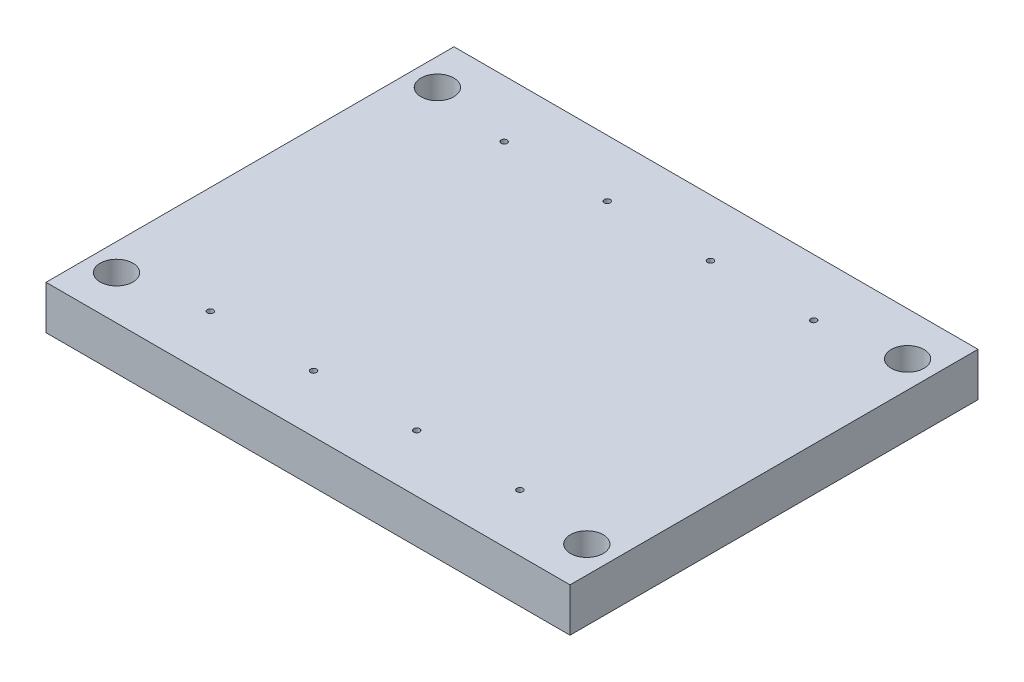
SolidWorks part; units mm, degrees
note: The reader was unsure of these and kept them because the rebuilt part matched: shared geometry of "Sketch1<3>".
ref_plane "Front" through (0, 0, 0) normal (0, 0, 1) x (1, 0, 0)
ref_plane "Top" through (0, 0, 0) normal (0, 1, 0) x (1, 0, 0)
ref_plane "Right" through (0, 0, 0) normal (1, 0, 0) x (0, 0, -1)
sketch "Sketch1" plane through (0, 0, 0) normal (0, 1, 0) x (1, 0, 0)
  line L0 (249.0003, 118.6422) -> (273.4797, 118.6422)
  line L1 (-44.4797, 118.6422) -> (249.0003, 118.6422)
  line L2 (-44.4797, 118.6422) -> (-44.4797, -118.6422)
  line L3 (-44.4797, -118.6422) -> (249.0003, -118.6422)
  line L4 (249.0003, 118.6422) -> (249.0003, -118.6422) construction
  line L5 (273.4797, 118.6422) -> (273.4797, -118.6422)
  line L6 (273.4797, -118.6422) -> (249.0003, -118.6422)
  line L7 (0, 92.9422) -> (-44.4797, 92.9422) construction
  line L8 (229, 92.9422) -> (273.4797, 92.9422) construction
  line B0 (0, 92.9422) -> (229, 92.9422) construction
  line B1 (0, 92.9422) -> (0, 77.9422) construction
  line B2 (0, 77.9422) -> (229, 77.9422) construction
  line B3 (229, 92.9422) -> (229, 77.9422) construction
  line B4 (0, -77.9422) -> (229, -77.9422) construction
  line B5 (0, -77.9422) -> (0, -92.9422) construction
  line B6 (0, -92.9422) -> (229, -92.9422) construction
  line B7 (229, -77.9422) -> (229, -92.9422) construction
  line B8 (0, 118.6422) -> (101.6, 118.6422) construction
  line B9 (0, 118.6422) -> (0, -118.6422) construction
  line B10 (0, -118.6422) -> (101.6, -118.6422) construction
  line B11 (101.6, 118.6422) -> (101.6, -118.6422) construction
  line B12 (249.0003, 8.5027) -> (229.0003, 8.5027) construction
  line B13 (249.0003, 8.5027) -> (249.0003, 68.5027) construction
  line B14 (249.0003, 68.5027) -> (229.0003, 68.5027) construction
  line B15 (229.0003, 8.5027) -> (229.0003, 68.5027) construction
  line B16 (-44.4797, 8.5027) -> (-19.4797, 8.5027) construction
  line B17 (-44.4797, 8.5027) -> (-44.4797, 68.5027) construction
  line B18 (-44.4797, 68.5027) -> (-19.4797, 68.5027) construction
  line B19 (-19.4797, 8.5027) -> (-19.4797, 68.5027) construction
  line B20 (-19.4797, 21.5027) -> (-14.3297, 21.5027) construction
  line B21 (-14.3297, 21.5027) -> (-14.3297, 30.5027) construction
  line B22 (-14.3297, 30.5027) -> (-7.9797, 30.5027) construction
  line B23 (-7.9797, 30.5027) -> (-7.9797, 14.5027) construction
  line B24 (-7.9797, 14.5027) -> (0, 14.5027) construction
  line B25 (0, 62.5027) -> (-7.9797, 62.5027) construction
  line B26 (-7.9797, 62.5027) -> (-7.9797, 46.5027) construction
  line B27 (-7.9797, 46.5027) -> (-14.3297, 46.5027) construction
  line B28 (-14.3297, 46.5027) -> (-14.3297, 55.5027) construction
  line B29 (-14.3297, 55.5027) -> (-19.4797, 55.5027) construction
  circle B30 centre (24.5, 85.4422) radius 1.75
  circle B31 centre (84.5, 85.4422) radius 1.75
  circle B32 centre (144.5, 85.4422) radius 1.75
  circle B33 centre (204.5, 85.4422) radius 1.75
  circle B34 centre (24.5, -85.4422) radius 1.75
  circle B35 centre (84.5, -85.4422) radius 1.75
  circle B36 centre (144.5, -85.4422) radius 1.75
  circle B37 centre (204.5, -85.4422) radius 1.75
  circle B38 centre (-25.4797, 15.5027) radius 3.3
  circle B39 centre (-38.4797, 15.5027) radius 3.3
  circle B40 centre (-25.4797, 61.5027) radius 3.3
  circle B41 centre (-38.4797, 61.5027) radius 3.3
  circle B42 centre (239.0003, 15.5027) radius 3.3
  circle B43 centre (239.0003, 61.5027) radius 3.3
sketch_block_instance "Block-TopView-1"
sketch_block "Block-TopView"
sketch "Sketch2" plane through (0, 0, 0) normal (0, 0, 1) x (1, 0, 0)
  line B0 (-24.4793, 87.9) -> (-24.4793, 25.4)
  line B1 (-24.4793, 25.4) -> (204.5207, 25.4)
  line B2 (204.5207, 25.4) -> (204.5207, 87.9)
  line B3 (249.0003, 87.9) -> (249.0003, 0)
  line B4 (249.0003, 0) -> (-44.4797, 0)
  line B5 (-44.4797, 0) -> (-44.4797, 87.9)
sketch_block_instance "Block-SideView-1"
sketch_block "Block-SideView" parameters "D1"=229
extrude "Boss-Extrude1" add sketch "Sketch1" along normal up to vertex (25.4 mm away) contours B41 | B40 | B38 | B39 | B30 | B31 | B33 | B32 | B43 | B42 | B34 | B35 | B36 | B37 | L4 L1 L2 L3 B43 B42 B41 B40 B39 B38 B37 B36 B35 B34 B33 B32 B31 B30
extrude "Cut-Extrude1" cut sketch "Sketch1<3>" against normal blind 6.35 from surface at 25.4 contours B30 | B31 | B32 | B33 | B34 | B35 | B36 | B37 starting at face at (114.5, 25.4, 0)
sketch "Sketch1<3>" plane through (0, 0, 0) normal (0, 1, 0) x (1, 0, 0) same geometry as "Sketch1"
sketch "Sketch5" plane through (0, 25.4, 0) normal (0, 1, 0) x (1, 0, 0)
  circle A0 centre (-22.2547, -93.2422) radius 9.525
  circle A1 centre (251.2547, -93.2422) radius 9.525
  circle A2 centre (251.2547, 93.3378) radius 9.525
  circle A3 centre (-22.2547, 93.3378) radius 9.525
  circle A4 centre (251.2547, -93.2422) radius 7.9375 construction
  circle A5 centre (251.2547, 93.3378) radius 7.9375 construction
  circle A6 centre (-22.2547, 93.3378) radius 7.9375 construction
  circle A7 centre (-22.2547, -93.2422) radius 7.9375 construction
  dimension "D1" = 19.05
extrude "Cut-Extrude2" cut sketch "Sketch5" against normal through all
sketch "Sketch6" plane through (0, 0, 118.6422) normal (0, 0, 1) x (1, 0, 0)
  line L0 (273.4797, 25.4) -> (-44.4797, 25.4) construction
  line L1 (-37.9, 25.4) -> (266.9, 25.4) construction
  line L2 (-37.9, 25.4) -> (-37.9, 0)
  line L3 (-37.9, 0) -> (266.9, 0) construction
  line L4 (266.9, 25.4) -> (266.9, 0)
  line L6 (114.5, 0) -> (114.5, 25.4) construction
  line L7 (-37.9, 25.4) -> (-49.6759, 25.4)
  line L8 (-49.6759, 25.4) -> (-49.6759, 0)
  line L9 (-49.6759, 0) -> (-37.9, 0)
  line L10 (266.9, 25.4) -> (278.0321, 25.4)
  line L11 (278.0321, 25.4) -> (278.0321, 0)
  line L12 (278.0321, 0) -> (266.9, 0)
  dimension "D1" = 304.8
extrude "Cut-Extrude3" cut sketch "Sketch6" against normal up to next
